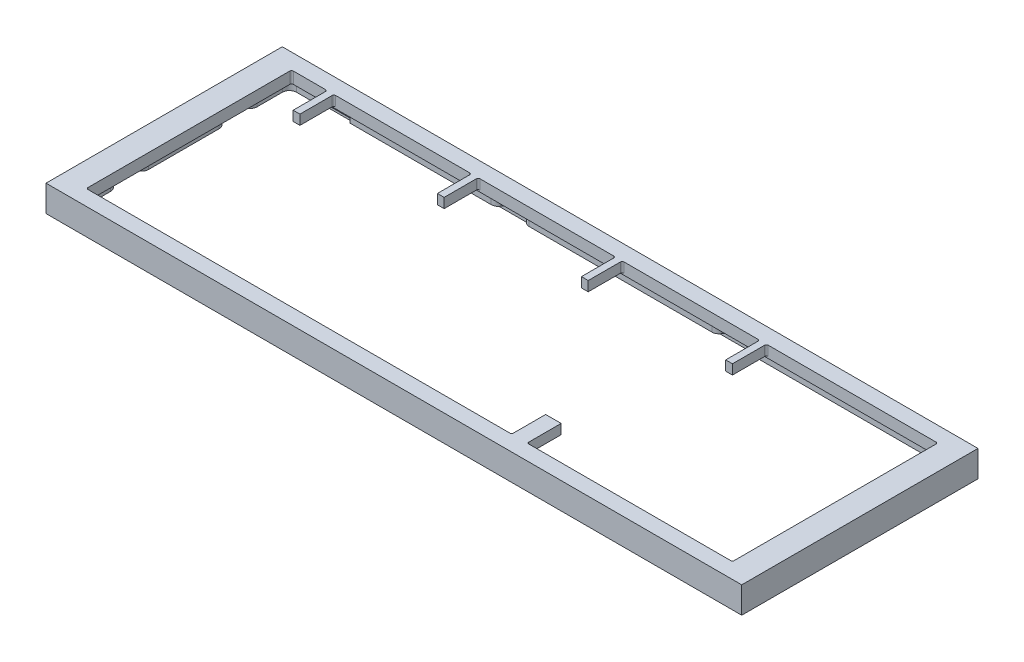
SolidWorks part; units mm, degrees
ref_plane "Front Plane" through (0, 0, 0) normal (0, 0, 1) x (1, 0, 0)
ref_plane "Top Plane" through (0, 0, 0) normal (0, 1, 0) x (1, 0, 0)
ref_plane "Right Plane" through (0, 0, 0) normal (1, 0, 0) x (0, 0, -1)
sketch "Sketch1" plane through (0, 0, 0) normal (0, 1, 0) x (1, 0, 0)
  line L1 (0, 0) -> (390.74, 0)
  line L2 (0, 0) -> (0, 132.7)
  line L3 (0, 132.7) -> (390.74, 132.7)
  line L4 (390.74, 0) -> (390.74, 132.7)
  line L5 (13.92, 124) -> (376.82, 124)
  line L6 (13.92, 124) -> (13.92, 8.7)
  line L7 (13.92, 8.7) -> (376.82, 8.7)
  line L8 (376.82, 124) -> (376.82, 8.7)
  point P9 (195.37, 124)
  point P10 (195.37, 132.7)
  point P11 (13.92, 66.35)
  point P12 (0, 66.35)
  dimension "D1" = 362.9
  dimension "D2" = 115.3
  dimension "D3" = 8.7
  dimension "D4" = 13.92
extrude "Main Body" add sketch "Sketch1" along normal blind 14.8
sketch "Sketch2" plane through (0, 0, 0) normal (0, -1, 0) x (1, 0, 0)
  line L0 (390.74, -132.7) -> (0, -132.7) construction
  line L1 (388.74, -130.7) -> (2, -130.7)
  line L2 (388.74, -130.7) -> (388.74, -2)
  line L3 (388.74, -2) -> (2, -2)
  line L4 (2, -130.7) -> (2, -2)
  line L5 (390.74, 0) -> (390.74, -132.7) construction
  point P4 (195.37, -130.7)
  point P7 (195.37, -132.7)
  point P8 (388.74, -66.35)
  point P11 (390.74, -66.35)
  dimension "D1" = 2
  dimension "D2" = 2
extrude "Alignment Guide" cut sketch "Sketch2" against normal blind 2 contours L2 L1 L4 L3
sketch "Sketch3" plane through (0, 14.8, 0) normal (0, 1, 0) x (1, 0, 0)
  line L0 (13.92, 8.7) -> (376.82, 8.7) construction
  line L1 (252.82, 27.8) -> (261.52, 27.8)
  line L2 (252.82, 27.8) -> (252.82, 8.7)
  line L3 (252.82, 8.7) -> (261.52, 8.7)
  line L4 (261.52, 27.8) -> (261.52, 8.7)
  line L5 (376.82, 8.7) -> (376.82, 124) construction
  line L6 (376.82, 124) -> (13.92, 124) construction
  line L7 (33.92, 124) -> (37.72, 124)
  line L8 (33.92, 124) -> (33.92, 104.9)
  line L9 (33.92, 104.9) -> (37.72, 104.9)
  line L10 (37.72, 124) -> (37.72, 104.9)
  line L11 (13.92, 124) -> (13.92, 8.7) construction
  line L12 (114.92, 124) -> (118.72, 124)
  line L13 (114.92, 124) -> (114.92, 104.9)
  line L14 (114.92, 104.9) -> (118.72, 104.9)
  line L15 (118.72, 124) -> (118.72, 104.9)
  line L16 (195.82, 124) -> (199.62, 124)
  line L17 (195.82, 124) -> (195.82, 104.9)
  line L18 (195.82, 104.9) -> (199.62, 104.9)
  line L19 (199.62, 124) -> (199.62, 104.9)
  line L20 (276.82, 124) -> (280.62, 124)
  line L21 (276.82, 124) -> (276.82, 104.9)
  line L22 (276.82, 104.9) -> (280.62, 104.9)
  line L23 (280.62, 124) -> (280.62, 104.9)
  point P8 (257.17, 8.7)
  dimension "D1" = 115.3
  dimension "D2" = 124
  dimension "D3" = 19.1
  dimension "D4" = 3.8
  dimension "D5" = 19.1
  dimension "D6" = 77.2
  dimension "D7" = 77.1
  dimension "D8" = 77.2
  dimension "D9" = 20
extrude "Blockers" add sketch "Sketch3" against normal blind 5.5
fillet "Fillet5" radius 1 14 edges at (280.62, 12.05, -124) (276.82, 12.05, -124) (195.82, 12.05, -124) (199.62, 12.05, -124) (118.72, 12.05, -124) (114.92, 12.05, -124) (33.92, 12.05, -124) (37.72, 12.05, -124) (13.92, 8.4, -124) (13.92, 8.4, -8.7) (252.82, 12.05, -8.7) (261.52, 12.05, -8.7) (376.82, 8.4, -8.7) (376.82, 8.4, -124)
sketch "Sketch4" plane through (0, 2, 0) normal (0, -1, 0) x (1, 0, 0)
  line L0 (0, 0) -> (390.74, 0) construction
  line L1 (381.37, -127.35) -> (9.37, -127.35)
  line L2 (381.37, -127.35) -> (381.37, -5.35)
  line L3 (381.37, -5.35) -> (9.37, -5.35)
  line L4 (9.37, -127.35) -> (9.37, -5.35)
  line L5 (390.74, 0) -> (390.74, -132.7) construction
  point P4 (195.37, -5.35)
  point P7 (195.37, 0)
  point P8 (381.37, -66.35)
  point P11 (390.74, -66.35)
  dimension "D1" = 122
  dimension "D2" = 372
extrude "PCB Cutout" cut sketch "Sketch4" against normal offset from surface (6.3 mm away) 6.5 up to face at (195.37, 14.8, -66.35)
fillet "Fillet4" radius 4 8 edges at (9.37, 5.15, -5.35) (9.37, 5.15, -127.35) (381.37, 5.15, -127.35) (381.37, 5.15, -5.35) (2, 1, -130.7) (2, 1, -2) (388.74, 1, -2) (388.74, 1, -130.7)
sketch "Sketch6" plane through (0, 2, 0) normal (0, -1, 0) x (1, 0, 0)
  line L0 (384.74, -130.7) -> (6, -130.7) construction
  line L1 (249.87, -130.7) -> (264.87, -130.7)
  line L2 (249.87, -130.7) -> (249.87, -127.35)
  line L3 (249.87, -127.35) -> (264.87, -127.35)
  line L4 (264.87, -130.7) -> (264.87, -127.35)
  line L5 (13.37, -127.35) -> (377.37, -127.35) construction
  line L6 (381.37, -9.35) -> (381.37, -123.35) construction
  line L7 (381.37, -106.025) -> (384.72, -106.025)
  line L8 (381.37, -106.025) -> (381.37, -91.025)
  line L9 (381.37, -91.025) -> (384.72, -91.025)
  line L10 (384.72, -106.025) -> (384.72, -91.025)
  line L11 (377.37, -5.35) -> (13.37, -5.35) construction
  line L12 (381.37, -45.025) -> (384.72, -45.025)
  line L13 (381.37, -45.025) -> (381.37, -30.025)
  line L14 (381.37, -30.025) -> (384.72, -30.025)
  line L15 (384.72, -45.025) -> (384.72, -30.025)
  line L16 (264.87, -5.35) -> (249.87, -5.35)
  line L17 (264.87, -5.35) -> (264.87, -2)
  line L18 (264.87, -2) -> (249.87, -2)
  line L19 (249.87, -5.35) -> (249.87, -2)
  line L20 (384.74, -2) -> (6, -2) construction
  line L21 (195.37, -132.7) -> (195.37, 0) construction
  line L22 (390.74, -132.7) -> (0, -132.7) construction
  line L23 (0, 0) -> (390.74, 0) construction
  line L24 (390.74, -66.35) -> (195.37, -66.35) construction
  line L25 (390.74, 0) -> (390.74, -132.7) construction
  line L26 (328.6755, -66.35) -> (328.6755, -130.7) construction
  line L27 (384.74, -130.7) -> (6, -130.7) construction
  line L28 (328.6755, -66.35) -> (328.6755, -8.7) construction
  line L29 (375.82, -8.7) -> (14.92, -8.7) construction
  line L30 (125.87, -2) -> (140.87, -2)
  line L31 (140.87, -5.35) -> (140.87, -2)
  line L32 (125.87, -5.35) -> (140.87, -5.35)
  line L33 (125.87, -5.35) -> (125.87, -2)
  line L34 (9.37, -30.025) -> (6.02, -30.025)
  line L35 (6.02, -45.025) -> (6.02, -30.025)
  line L36 (9.37, -45.025) -> (6.02, -45.025)
  line L37 (9.37, -45.025) -> (9.37, -30.025)
  line L38 (9.37, -91.025) -> (6.02, -91.025)
  line L39 (6.02, -106.025) -> (6.02, -91.025)
  line L40 (9.37, -106.025) -> (6.02, -106.025)
  line L41 (9.37, -106.025) -> (9.37, -91.025)
  line L42 (140.87, -127.35) -> (125.87, -127.35)
  line L43 (125.87, -130.7) -> (125.87, -127.35)
  line L44 (140.87, -130.7) -> (125.87, -130.7)
  line L45 (140.87, -130.7) -> (140.87, -127.35)
  line L46 (381.37, -123.35) -> (381.37, -9.35) construction
  point P32 (257.37, -127.35)
  point P33 (257.37, -5.35)
  point P46 (381.37, -37.525)
  point P47 (328.6755, -37.525)
  point P48 (381.37, -98.525)
  point P49 (328.6755, -98.525)
  dimension "D1" = 15
  dimension "D2" = 124
extrude "PlateTabs" cut sketch "Sketch6" against normal up to surface (6.3 mm away) up to face at (195.37, 8.3, -66.35)
fillet "Fillet2" radius 2.5 16 edges at (249.87, 5.15, -2) (264.87, 5.15, -2) (140.87, 5.15, -2) (125.87, 5.15, -2) (6.02, 5.15, -30.025) (6.02, 5.15, -45.025) (6.02, 5.15, -91.025) (6.02, 5.15, -106.025) (140.87, 5.15, -130.7) (125.87, 5.15, -130.7) (249.87, 5.15, -130.7) (264.87, 5.15, -130.7) (384.72, 5.15, -45.025) (384.72, 5.15, -30.025) (384.72, 5.15, -91.025) (384.72, 5.15, -106.025)
fillet "Fillet3" radius 4 16 edges at (381.37, 5.15, -30.025) (381.37, 5.15, -45.025) (381.37, 5.15, -91.025) (381.37, 5.15, -106.025) (249.87, 5.15, -5.35) (264.87, 5.15, -5.35) (140.87, 5.15, -5.35) (125.87, 5.15, -5.35) (9.37, 5.15, -30.025) (9.37, 5.15, -45.025) (9.37, 5.15, -91.025) (9.37, 5.15, -106.025) (125.87, 5.15, -127.35) (140.87, 5.15, -127.35) (249.87, 5.15, -127.35) (264.87, 5.15, -127.35)
sketch "Sketch9" plane through (0, 0, -132.7) normal (0, 0, -1) x (-1, 0, 0)
  line L1 (-40.9, 3) -> (-30.9, 3)
  line L2 (-40.9, 3) -> (-40.9, 6.8)
  line L3 (-40.9, 6.8) -> (-30.9, 6.8)
  line L4 (-30.9, 3) -> (-30.9, 6.8)
  line L7 (0, 14.8) -> (0, 0) construction
  line L8 (-390.74, 0) -> (0, 0) construction
  point P4 (-30.9, 4.9)
  point P6 (-35.9, 6.8)
  point P10 (-40.9, 0.4236)
  dimension "D1" = 4.9
  dimension "D2" = 3.8
  dimension "D3" = 10
  dimension "D4" = 35.9
extrude "USB Cutout" cut sketch "Sketch9" against normal up to surface (8.7 mm away) up to face at (164.89, 11.95, -124)
sketch "Sketch10" plane through (0, 0, -132.7) normal (0, 0, -1) x (-1, 0, 0)
  line L0 (-30.9, 6.8) -> (-40.9, 6.8) construction
  line L1 (-42.9, 8.8) -> (-28.9, 8.8)
  line L2 (-42.9, 8.8) -> (-42.9, 1)
  line L3 (-42.9, 1) -> (-28.9, 1)
  line L4 (-28.9, 8.8) -> (-28.9, 1)
  line L5 (-40.9, 6.8) -> (-40.9, 3) construction
  point P4 (-35.9, 8.8)
  point P7 (-35.9, 6.8)
  point P10 (-40.9, 4.9)
  point P11 (-42.9, 4.9)
  dimension "D1" = 2
  dimension "D2" = 2
extrude "USB Outline" cut sketch "Sketch10" against normal blind 1
sketch "Sketch11" plane through (0, 0, -127.35) normal (0, 0, 1) x (1, 0, 0)
  line L0 (13.37, 2) -> (122.6843, 2) construction
  line L1 (43.4, 2) -> (28.4, 2)
  line L2 (43.4, 2) -> (43.4, 6.8)
  line L3 (43.4, 6.8) -> (28.4, 6.8)
  line L4 (28.4, 2) -> (28.4, 6.8)
  line L5 (30.9, 6.8) -> (40.9, 6.8) construction
  line L6 (40.9, 3) -> (30.9, 3) construction
  point P8 (35.9, 2)
  point P11 (35.9, 3)
  dimension "D1" = 15
extrude "PCB Clearance" cut sketch "Sketch11" against normal blind 2.5
fillet "Fillet6" radius 1.5 8 edges at (40.9, 6.8, -130.775) (30.9, 6.8, -130.775) (40.9, 3, -130.775) (42.9, 1, -132.2) (42.9, 8.8, -132.2) (28.9, 8.8, -132.2) (30.9, 3, -130.775) (28.9, 1, -132.2)
fillet "Fillet7" radius 2.5 2 edges at (28.4, 4.4, -129.85) (43.4, 4.4, -129.85)
sketch "Sketch12" plane through (0, 8.3, 0) normal (0, -1, 0) x (1, 0, 0)
  line L0 (262.37, -130.7) -> (252.37, -130.7) construction
  line L1 (252.37, -2) -> (262.37, -2) construction
  line L3 (384.72, -42.525) -> (384.72, -32.525) construction
  line L4 (384.72, -93.525) -> (384.72, -103.525) construction
  line L5 (195.37, -132.7) -> (195.37, 0) construction
  line L6 (390.74, -132.7) -> (0, -132.7) construction
  line L7 (0, 0) -> (390.74, 0) construction
  point P0 (257.37, -127.8)
  point P1 (381.82, -98.525)
  point P2 (381.82, -37.525)
  point P3 (257.37, -4.9)
  point P6 (133.37, -4.9)
  point P9 (8.92, -37.525)
  point P10 (257.37, -2)
  point P11 (8.92, -98.525)
  point P14 (384.72, -37.525)
  point P15 (133.37, -127.8)
  point P18 (384.72, -98.525)
  dimension "D1" = 2.9
  dimension "D2" = 2.9
  dimension "D4" = 2.9
sketch "Sketch14" plane through (0, 2, 0) normal (0, -1, 0) x (1, 0, 0)
  line L0 (195.37, -132.7) -> (195.37, 0) construction
  line L1 (390.74, -132.7) -> (0, -132.7) construction
  line L2 (0, 0) -> (390.74, 0) construction
  line L5 (195.37, -66.35) -> (390.74, -66.35) construction
  line L6 (390.74, 0) -> (390.74, -132.7) construction
  line L7 (388.74, -126.7) -> (388.74, -6) construction
  line L8 (384.74, -130.7) -> (6, -130.7) construction
  line L9 (384.74, -2) -> (262.37, -2) construction
  point P6 (0, 0)
  point P8 (385.04, -111.35)
  point P9 (385.04, -66.35)
  point P10 (385.04, -21.35)
  point P11 (280.74, -3.7)
  point P20 (280.74, -129)
  point P21 (0, 0)
  point P22 (110, -3.7)
  point P23 (0, 0)
  point P24 (0, 0)
  point P25 (0, 0)
  point P28 (110, -129)
  point P29 (5.7, -21.35)
  point P30 (5.7, -66.35)
  point P31 (5.7, -111.35)
  point P32 (0, 0)
  dimension "D1" = 1.7
  dimension "D2" = 1.7
  dimension "D3" = 110
  dimension "D4" = 45
  dimension "D5" = 45
  dimension "D6" = 3.7
hole_wizard "M2x0.4 Tapped Hole1" positions "3DSketch2" profile "Sketch16" tap size "M2x0.4" standard "ANSI Metric"
sketch3d "3DSketch2"
  point P0 (385.04, 2, -111.35)
  point P3 (381.82, 8.3, -98.525)
  point P6 (381.82, 8.3, -37.525)
  point P9 (385.04, 2, -21.35)
  point P12 (385.04, 2, -66.35)
  point P15 (280.74, 2, -3.7)
  point P18 (257.37, 8.3, -4.9)
  point P21 (133.37, 8.3, -4.9)
  point P24 (110, 2, -3.7)
  point P27 (5.7, 2, -21.35)
  point P30 (8.92, 8.3, -37.525)
  point P33 (5.7, 2, -66.35)
  point P36 (8.92, 8.3, -98.525)
  point P39 (5.7, 2, -111.35)
  point P42 (110, 2, -129)
  point P45 (133.37, 8.3, -127.8)
  point P48 (257.37, 8.3, -127.8)
  point P51 (280.74, 2, -129)
sketch "Sketch16" plane through (385.04, 2, -111.35) normal (1, 0, 0) x (0, 0, -1)
  line L0 (0, 0) -> (0, 4.4807)
  line L1 (0, 4.4807) -> (0.8, 4)
  line L2 (0.8, 4) -> (0.8, 0)
  line L5 (0.8, 0) -> (0, 0)
  line L10 (0, 4.4807) -> (-0.8, 4) construction
  line L11 (0, -6.35) -> (0, 107.95) construction
  dimension "Tap Drill Dia." = 1.6
  dimension "Tap Drill Depth" = 4
  dimension "Drill Angle" = 118
cosmetic thread "Hole Thread20" parameters "D1"=4, "D2"=2
cosmetic thread "Hole Thread21" parameters "D1"=4, "D2"=2
cosmetic thread "Hole Thread22" parameters "D1"=4, "D2"=2
cosmetic thread "Hole Thread23" parameters "D1"=4, "D2"=2
cosmetic thread "Hole Thread24" parameters "D1"=4, "D2"=2
cosmetic thread "Hole Thread25" parameters "D1"=4, "D2"=2
cosmetic thread "Hole Thread26" parameters "D1"=4, "D2"=2
cosmetic thread "Hole Thread27" parameters "D1"=4, "D2"=2
cosmetic thread "Hole Thread28" parameters "D1"=4, "D2"=2
cosmetic thread "Hole Thread29" parameters "D1"=4, "D2"=2
cosmetic thread "Hole Thread30" parameters "D1"=4, "D2"=2
cosmetic thread "Hole Thread31" parameters "D1"=4, "D2"=2
cosmetic thread "Hole Thread32" parameters "D1"=4, "D2"=2
cosmetic thread "Hole Thread33" parameters "D1"=4, "D2"=2
cosmetic thread "Hole Thread34" parameters "D1"=4, "D2"=2
cosmetic thread "Hole Thread35" parameters "D1"=4, "D2"=2
cosmetic thread "Hole Thread36" parameters "D1"=4, "D2"=2
cosmetic thread "Hole Thread37" parameters "D1"=4, "D2"=2
